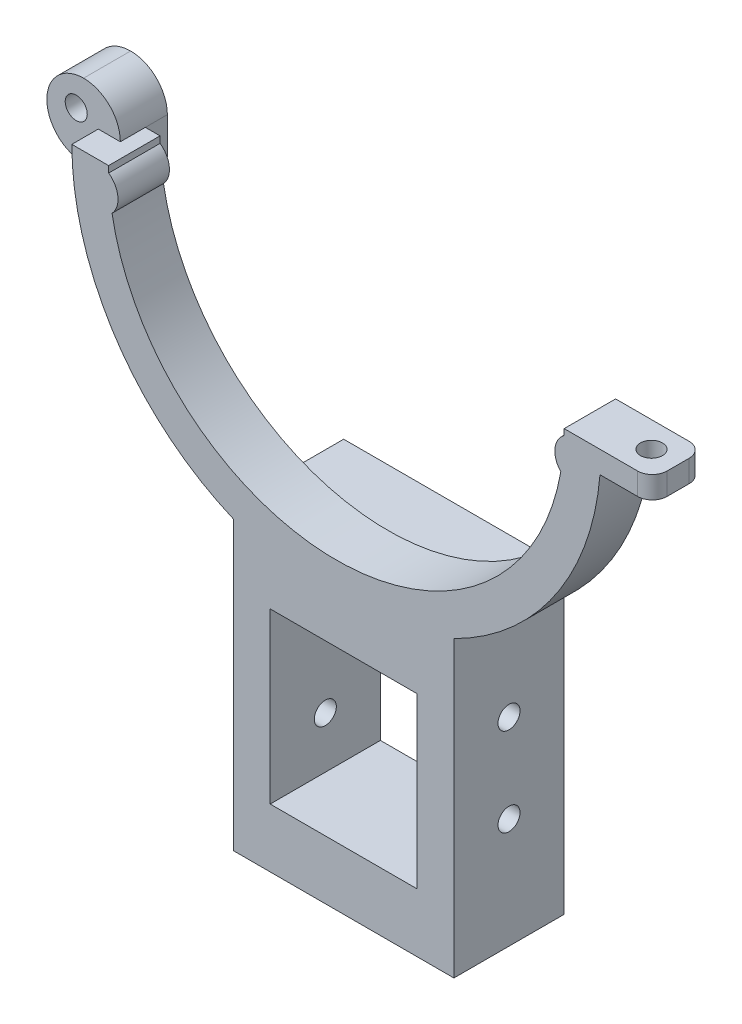
SolidWorks part; units mm, degrees
ref_plane "Front Plane" through (0, 0, 0) normal (0, 0, 1) x (1, 0, 0)
ref_plane "Top Plane" through (0, 0, 0) normal (0, 1, 0) x (1, 0, 0)
ref_plane "Right Plane" through (0, 0, 0) normal (1, 0, 0) x (0, 0, -1)
sketch "Sketch1" plane through (0, 0, 0) normal (0, 0, 1) x (1, 0, 0)
  line L0 (-36, 0) -> (36, 0)
  line L3 (-14.007, -33.1633) -> (-14.007, -72.2525)
  line L4 (-14.007, -72.2525) -> (15.993, -72.2525)
  line L5 (15.993, -32.2525) -> (15.993, -72.2525)
  circle A0 centre (0, 0) radius 31
  circle A1 centre (0, 0) radius 36
  circle A2 centre (-32.7163, -3.3335) radius 3
  circle A3 centre (32.7313, -3.2727) radius 3
  dimension "D2" = 62
  dimension "D3" = 0
  dimension "D4" = 72
  dimension "D8" = 6
  dimension "D9" = 6
  dimension "D1" = 0
  dimension "D5" = 36
  dimension "D6" = 36
  dimension "D7" = 0
  dimension "D10" = 36
  dimension "D11" = 36
  dimension "D12" = 30
  dimension "D13" = 90
  dimension "D14" = 40
extrude "Boss-Extrude2" add sketch "Sketch1" along normal blind 7 contours A0 A3 | A0 A3 | A3 A0 A2 L0 A1 | A0 A2 L0 | A0 A2 | A1 L3 L4 L5 region at (33.5, -0.0805, 0) region at (33.0577, -3.3053, 0) region at (30.3825, -3.0379, 0) region at (1.0516, -53.5699, 0) region at (-30.373, -3.0948, 0) region at (-33.0462, -3.3672, 0)
sketch "Sketch2" plane through (0, 0, 0) normal (0, 0, -1) x (-1, 0, 0)
  line L0 (36, 0) -> (31, 0) construction
  line L1 (33, 5) -> (43, 5)
  line L2 (33, 5) -> (33, -5)
  line L3 (33, -5) -> (43, -5)
  line L4 (43, 5) -> (43, -5)
  dimension "D1" = 5
  dimension "D2" = 10
  dimension "D3" = 10
  dimension "D4" = 2
extrude "Boss-Extrude4" add sketch "Sketch2" against normal blind 3.4 and the other way blind 3
sketch "Sketch3" plane through (0, 0, 3.4) normal (0, 0, 1) x (1, 0, 0)
  line L0 (-43, 5) -> (-33, 5) construction
  line L1 (-43, -5) -> (-43, 5) construction
  circle A0 centre (-39, 1) radius 1.5
  dimension "D1" = 3
  dimension "D2" = 4
  dimension "D3" = 4
extrude "Cut-Extrude1" cut sketch "Sketch3" against normal blind 10
sketch "Sketch4" plane through (0, 0, 0) normal (0, 0, -1) x (-1, 0, 0)
  line L0 (-31, 0) -> (-36, 0) construction
  line L1 (-35, 0) -> (-43, 0)
  line L2 (-35, 0) -> (-35, -3)
  line L3 (-35, -3) -> (-43, -3)
  line L4 (-43, 0) -> (-43, -3)
  dimension "D1" = 4
  dimension "D2" = 0
  dimension "D3" = 3
  dimension "D4" = 8
extrude "Boss-Extrude5" add sketch "Sketch4" against normal blind 7
sketch "Sketch5" plane through (0, -3, 0) normal (0, -1, 0) x (1, 0, 0)
  line L0 (43, 7) -> (35.8748, 7) construction
  line L1 (35.8748, 0) -> (35.8748, 7) construction
  circle A0 centre (39.3748, 3.5) radius 1.5
  dimension "D1" = 3
  dimension "D2" = 3.5
  dimension "D3" = 3.5
extrude "Cut-Extrude2" cut sketch "Sketch5" against normal blind 7
fillet "Fillet1" radius 5 1 edges at (-43, -5, 0.2) type face fillet first side face at (-43, 0, 0.2) second side face at (-37.217, -5, 0.1333)
fillet "Fillet2" radius 5 1 edges at (-43, 5, 0.2) type face fillet first side face at (-38, 5, 0.2) second side face at (-43, 2.5, 0.2)
fillet "Fillet3" radius 5 1 edges at (-33, 5, 0.2) type face fillet first side face at (-35.5, 5, 0.2) second side face at (-33, 0, 0.1333)
fillet "Fillet4" radius 2 1 edges at (43, -1.5, 0) type face fillet first side face at (43, -1.5, 3.5) second side face at (1.523, -16.8279, 0)
fillet "Fillet5" radius 2 1 edges at (43, -1.5, 7) type face fillet first side face at (6.3383, -18.5504, 7) second side face at (43, -1.5, 4.5)
sketch "Sketch6" plane through (0, 0, 0) normal (0, 0, -1) x (-1, 0, 0)
  line L0 (14.007, -72.2525) -> (-15.993, -72.2525) construction
  line L1 (-15.993, -31.2525) -> (14.007, -31.2525)
  line L2 (-15.993, -31.2525) -> (-15.993, -72.2525)
  line L3 (-15.993, -72.2525) -> (14.007, -72.2525)
  line L4 (14.007, -31.2525) -> (14.007, -72.2525)
  line L5 (-15.993, -32.2525) -> (-15.993, -72.2525) construction
  line L6 (14.007, -33.1633) -> (14.007, -72.2525) construction
  dimension "D1" = 0
  dimension "D2" = 0
  dimension "D3" = 0
  dimension "D4" = 41
extrude "Boss-Extrude6" add sketch "Sketch6" along normal blind 8
sketch "Sketch7" plane through (0, 0, -8) normal (0, 0, -1) x (-1, 0, 0)
  line L0 (14.007, -31.2525) -> (-15.993, -31.2525) construction
  line L1 (-10.993, -41.2525) -> (9.007, -41.2525)
  line L2 (-10.993, -41.2525) -> (-10.993, -64.2525)
  line L3 (-10.993, -64.2525) -> (9.007, -64.2525)
  line L4 (9.007, -41.2525) -> (9.007, -64.2525)
  line L5 (-15.993, -31.2525) -> (-15.993, -72.2525) construction
  line L6 (14.007, -72.2525) -> (14.007, -31.2525) construction
  line L7 (-15.993, -72.2525) -> (14.007, -72.2525) construction
  dimension "D1" = 10
  dimension "D2" = 5
  dimension "D3" = 5
  dimension "D4" = 8
extrude "Cut-Extrude3" cut sketch "Sketch7" against normal blind 24
sketch "Sketch8" plane through (15.993, 0, 0) normal (1, 0, 0) x (0, 0, -1)
  line L1 (8, -31.2525) -> (8, -72.2525) construction
  line L2 (-7, -72.2525) -> (8, -72.2525) construction
  circle A0 centre (0.5, -45.2525) radius 1.5
  circle A1 centre (0.5, -57.2525) radius 1.5
  dimension "D1" = 3
  dimension "D2" = 7.5
  dimension "D3" = 27
  dimension "D4" = 3
  dimension "D5" = 7.5
  dimension "D6" = 15
extrude "Cut-Extrude5" cut sketch "Sketch8" against normal blind 54
